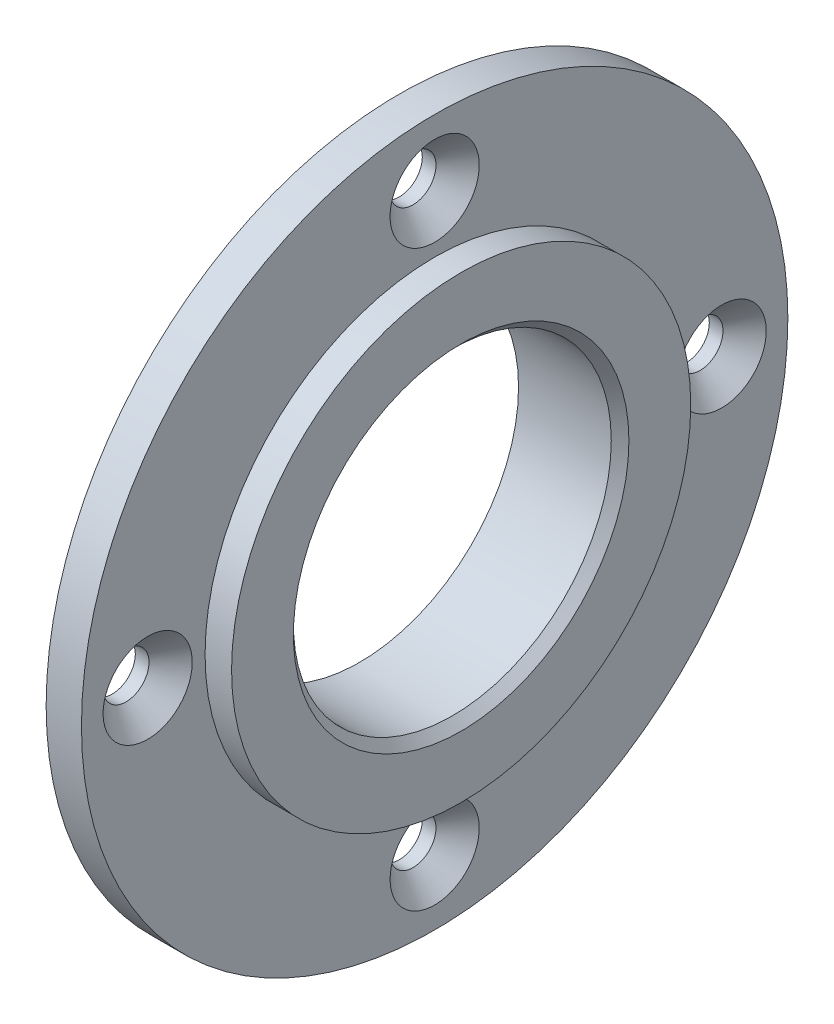
SolidWorks part; units mm, degrees
ref_plane "Front Plane" through (0, 0, 0) normal (0, 0, 1) x (1, 0, 0)
ref_plane "Top Plane" through (0, 0, 0) normal (0, 1, 0) x (1, 0, 0)
ref_plane "Right Plane" through (0, 0, 0) normal (1, 0, 0) x (0, 0, -1)
sketch "Sketch2" plane through (0, 0, 0) normal (0, 0, 1) x (1, 0, 0)
  line L0 (-174.9056, 26) -> (-177.9056, 26)
  line L1 (-177.9056, 26) -> (-177.9056, 40)
  line L2 (-177.9056, 40) -> (-181.9056, 40)
  line L3 (-181.9056, 40) -> (-181.9056, 21)
  line L4 (-186.4056, 18) -> (-174.9056, 18)
  line L5 (-174.9056, 18) -> (-174.9056, 26)
  line L6 (0, 0) -> (-61.0884, 0) construction
  line L7 (-182.4056, 18.3985) -> (-182.4056, 31.2775) construction
  line L8 (-181.9056, 21) -> (-186.4056, 21)
  line L9 (-186.4056, 21) -> (-186.4056, 18)
  line L14 (-198.4056, -21) -> (-198.4056, 21) construction
  dimension "D1" = 4
  dimension "D2" = 42
  dimension "D3" = 36
  dimension "D5" = 3
  dimension "D6" = 80
  dimension "D8" = 12
  dimension "D4" = 0.5
  dimension "D7" = 52
revolve "Revolve1" add sketch "Sketch2" angle 360 about L6
sketch "Sketch3" plane through (-177.9056, 0, 0) normal (1, 0, 0) x (0, 0, -1)
  circle A0 centre (0, 0) radius 32.5 construction
  circle A1 centre (0, 32.5) radius 3.3774
  dimension "D1" = 65
hole_wizard "CSK for M5 Countersunk Flat Head Screw1" positions "Sketch4" profile "Sketch5" countersink size "M5" standard "ISO" end condition through all
sketch "Sketch4" plane through (-177.9056, 0, 0) normal (1, 0, 0) x (0, 0, -1)
  point P0 (0, 32.5)
sketch "Sketch5" plane through (-177.9056, 32.5, 0) normal (0, 1, 0) x (0, 0, -1)
  line L0 (0, 0) -> (0, 8.5)
  line L1 (0, 8.5) -> (2.6, 8.5)
  line L2 (2.6, 8.5) -> (2.6, 2.45)
  line L3 (2.6, 2.45) -> (5.05, 0)
  line L5 (5.05, 0) -> (0, 0)
  line L6 (-2.6, 2.45) -> (-5.05, 0) construction
  line L11 (0, -6.35) -> (0, 107.95) construction
  dimension "Thru Hole Dia." = 5.2
  dimension "Thru Hole Depth" = 8.5
  dimension "Near C'Sink Dia." = 10.1
  dimension "Near C'Sink Angle" = 90
pattern_circular "CirPattern1" count 4 over 360 about axis through (0, 0, 0) along (1, 0, 0) of "CSK for M5 Countersunk Flat Head Screw1"
chamfer "Chamfer1" distance 0.5 angle 45 1 edges at (-186.4056, 0, -21)
chamfer "Chamfer2" distance 1 angle 45 1 edges at (-174.9056, 0, -18)
equation "\"l-x_vis_flasque_rouleau\"=4"
equation "\"D1@Sketch2\"= \"l-x_vis_flasque_rouleau\""
equation "\"d_ext_rouleau\"= 90"
equation "\"epaisseur_rouleau\"=80"
equation "\"alesage-rouleau\"= 52"
equation "\"jeu_dent_rouleau\"= 2"
equation "\"profondeur_dent_rouleau\"=4"
equation "\"n_dent_roueau\"= 15"
equation "\"B_roulement_rouleau\"= 12"
equation "\"F_anneau_alesage_rouleau\"=1.85"
equation "\"G_anneau_alesage_rouleau\"=47.5"
equation "\"K_anneau_alesage_rouleau\"=3.75"
equation "\"d_vis_flasque_rouleau\"=5"
equation "\"D2@Sketch2\" = \"d_ext_roulement_rouleau\""
equation "\"D3@Sketch2\"= \"d_ext_roulement_rouleau\" - 6"
equation "\"D8@Sketch2\"=\"B_roulement_rouleau\""
equation "\"g_anneau_arbre_rouleau\"=19"
equation "\"f_anneau_arbre_rouleau\"=1.3"
equation "\"k_anneau_arbre_rouleau\"=1.5"
equation "\"h_matrice\"= 22"
equation "\"d_matrice\"= 220"
equation "\"d_granulat\"= 8"
equation "\"zone_vide_matrice\" = 48"
equation "\"d_alesage_matrice\"=20"
equation "\"a_clavette_alesage_matrice\"=6"
equation "\"entrax_vis_rouleau\"=65"
equation "\"d_ext_roulement_rouleau\"= 42"
equation "\"d_int_roulement_rouleau\"= 20"
equation "\"D1@Sketch3\"=\"entrax_vis_rouleau\""
equation "\"D6@Sketch2\"=\"d_ext_rouleau\"-10"
equation "\"D7@Sketch2\"=\"alesage-rouleau\""
